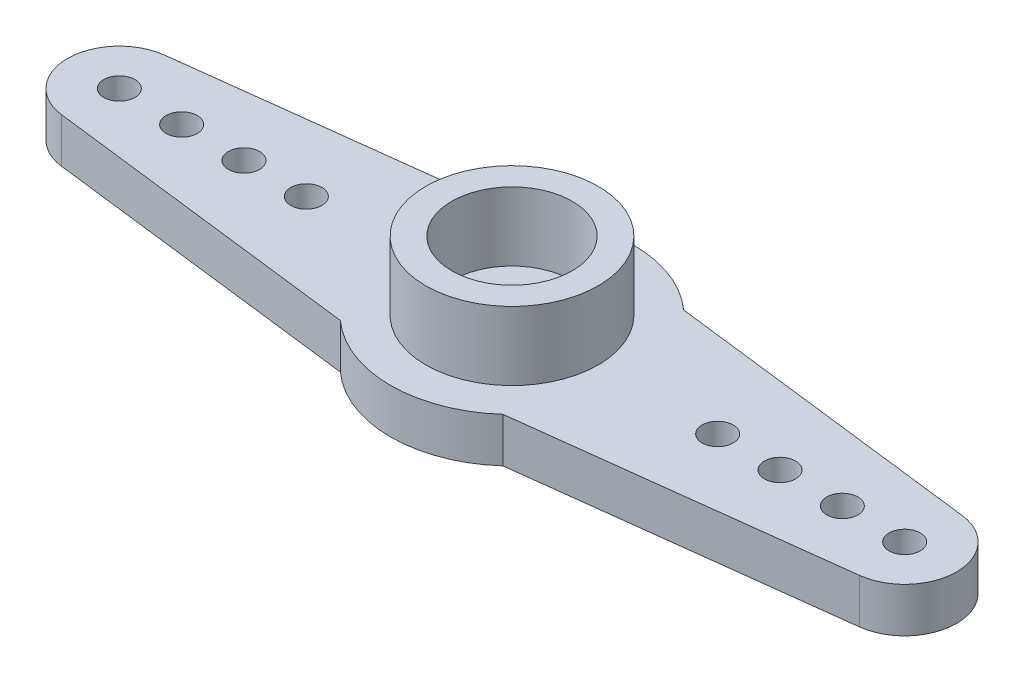
SolidWorks part; units mm, degrees
ref_plane "Front Plane" through (0, 0, 0) normal (0, 0, 1) x (1, 0, 0)
ref_plane "Top Plane" through (0, 0, 0) normal (0, 1, 0) x (1, 0, 0)
ref_plane "Right Plane" through (0, 0, 0) normal (1, 0, 0) x (0, 0, -1)
sketch "Sketch1" plane through (0, 0, 0) normal (0, 1, 0) x (1, 0, 0)
  line L0 (0, 18.3078) -> (0, -20.904) construction
  line L1 (-19.2032, 2.4815) -> (-3.9115, 4.35)
  line L2 (-19.2032, -2.4815) -> (-3.9115, -4.35)
  line L3 (-18.9, 0) -> (0, 0) construction
  line L4 (19.2032, -2.4815) -> (3.9115, -4.35)
  line L5 (19.2032, 2.4815) -> (3.9115, 4.35)
  circle A0 centre (0, 0) radius 5.85
  circle A1 centre (0, 0) radius 1.25
  arc A2 (-19.2032, -2.4815) -> (-19.2032, 2.4815) centre (-18.9, 0) cw
  circle A3 centre (-18.9, 0) radius 0.75
  circle A4 centre (-15.9, 0) radius 0.75
  circle A5 centre (-12.9, 0) radius 0.75
  circle A6 centre (-9.9, 0) radius 0.75
  circle A7 centre (9.9, 0) radius 0.75
  circle A8 centre (12.9, 0) radius 0.75
  circle A9 centre (15.9, 0) radius 0.75
  circle A10 centre (18.9, 0) radius 0.75
  arc A11 (19.2032, -2.4815) -> (19.2032, 2.4815) centre (18.9, 0) ccw
  dimension "D1" = 2.5
  dimension "D2" = 1.5
  dimension "D3" = 1.5
  dimension "D4" = 1.5
  dimension "D5" = 1.5
  dimension "D9" = 11.7
  dimension "D11" = 37.8
  dimension "D12" = 2.5
  dimension "D6" = 3
  dimension "D7" = 3
  dimension "D8" = 3
  dimension "D10" = 8.7
extrude "Boss-Extrude1" add sketch "Sketch1" along normal blind 2.15 contours A0 A1 | A2 L2 A0 L1 A6 A5 A4 A3 | L4 A11 L5 A0 A10 A8 A7 A9 region at (-11.5337, 0, -3.2219) region at (0, 0, -5.6845) region at (11.5337, 0, -3.2219)
sketch "Sketch2" plane through (0, 2.15, 0) normal (0, 1, 0) x (1, 0, 0)
  circle A0 centre (0, 0) radius 2.9
  circle A1 centre (0, 0) radius 4.15
  dimension "D1" = 8.3
  dimension "D2" = 5.8
extrude "Boss-Extrude2" add sketch "Sketch2" along normal blind 3.3
